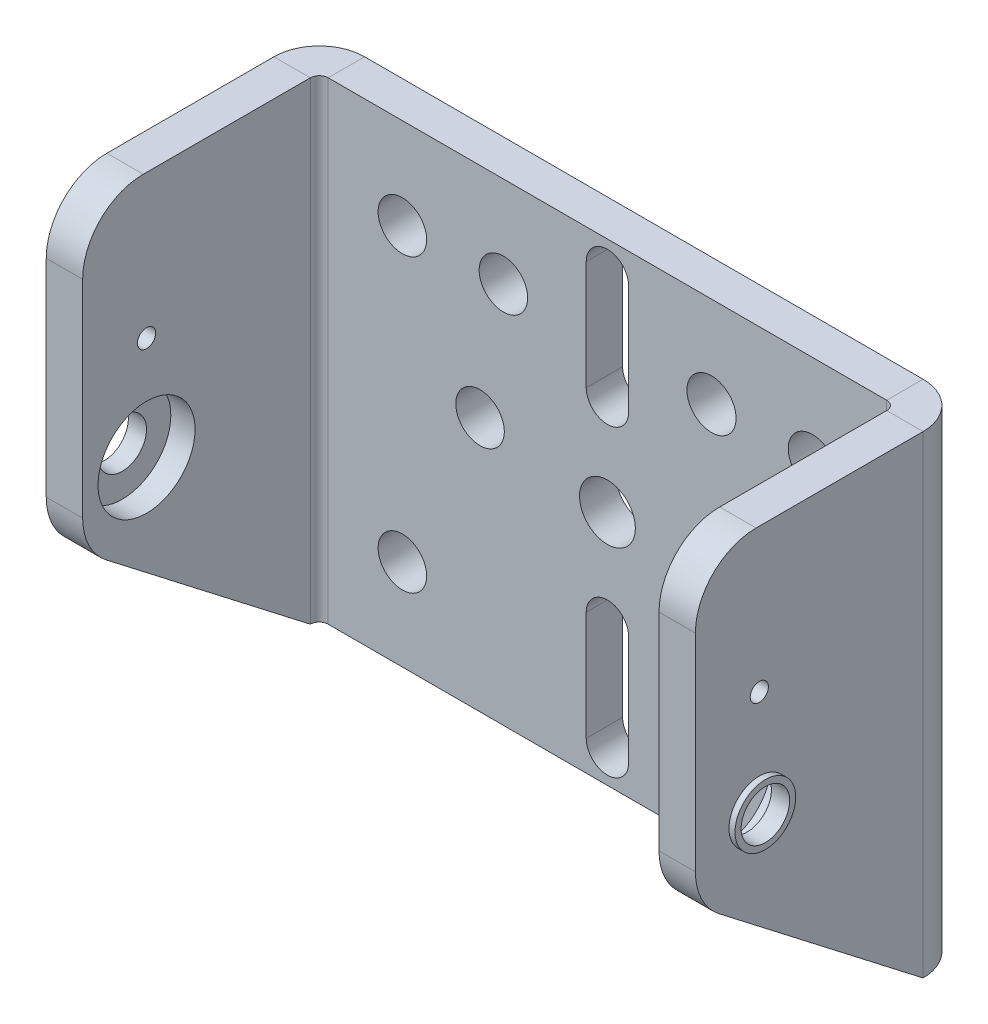
SolidWorks part; units mm, degrees
note: The reader was unsure of these and kept them because the rebuilt part matched: flange length of "Aresta-Flange1".
ref_plane "Plano frontal" through (0, 0, 0) normal (0, 0, 1) x (1, 0, 0)
ref_plane "Plano superior" through (0, 0, 0) normal (0, 1, 0) x (1, 0, 0)
ref_plane "Plano direito" through (0, 0, 0) normal (1, 0, 0) x (0, 0, -1)
sketch "Esboço1" plane through (0, 0, 0) normal (0, 0, 1) x (1, 0, 0)
  line L1 (-20.5063, 15.0091) -> (26.9937, 15.0091)
  line L2 (-20.5063, 15.0091) -> (-20.5063, -23.9909)
  line L3 (-20.5063, -23.9909) -> (26.9937, -23.9909)
  line L4 (26.9937, 15.0091) -> (26.9937, -23.9909)
  dimension "D1" = 47.5
  dimension "D2" = 39
base flange "Flange-base1" sketch "Esboço1" thickness 3 reverse thickness direction no parameters "D1"=0.7366
sketch "Esboço6" plane through (0, 0, 0) normal (0, 0, 1) x (1, 0, 0)
  line L1 (-13.6563, 7.5091) -> (20.1437, 7.5091)
  line L2 (-13.6563, 7.5091) -> (-13.6563, -16.4909)
  line L3 (-13.6563, -16.4909) -> (20.1437, -16.4909)
  line L4 (20.1437, 7.5091) -> (20.1437, -16.4909)
  line L6 (26.9937, 15.0091) -> (-20.5063, 15.0091) construction
  line L7 (-20.5063, -23.9909) -> (26.9937, -23.9909) construction
  line L8 (3.2437, 15.0091) -> (3.2437, -23.9909) construction
  line L9 (3.2437, 3.5238) -> (3.2437, 12.5238) construction
  line L10 (1.4937, 3.5238) -> (1.4937, 12.5238)
  line L11 (4.9937, 3.5238) -> (4.9937, 12.5238)
  line L12 (-20.5063, -4.4909) -> (26.9937, -4.4909) construction
  line L13 (-20.5063, 15.0091) -> (-20.5063, -23.9909) construction
  line L14 (26.9937, -23.9909) -> (26.9937, 15.0091) construction
  line L15 (3.2437, -12.5057) -> (3.2437, -21.5057) construction
  line L16 (1.4937, -12.5057) -> (1.4937, -21.5057)
  line L17 (4.9937, -12.5057) -> (4.9937, -21.5057)
  circle A0 centre (-13.6563, 7.5091) radius 2
  circle A1 centre (-13.6563, -16.4909) radius 2
  circle A2 centre (20.1437, -16.4909) radius 2
  circle A3 centre (20.1437, 7.5091) radius 2
  circle A4 centre (3.2437, -4.4909) radius 2.3
  arc A5 (1.4937, 3.5238) -> (4.9937, 3.5238) centre (3.2437, 3.5238) ccw
  arc A6 (4.9937, 12.5238) -> (1.4937, 12.5238) centre (3.2437, 12.5238) ccw
  arc A7 (1.4937, -12.5057) -> (4.9937, -12.5057) centre (3.2437, -12.5057) cw
  arc A8 (4.9937, -21.5057) -> (1.4937, -21.5057) centre (3.2437, -21.5057) cw
  point P18 (3.2437, 8.0238)
  point P31 (3.2437, -17.0057)
  dimension "D1" = 6.85
  dimension "D3" = 7.5
  dimension "D4" = 7.5
extrude "Corte-extrusão1" cut sketch "Esboço6" against normal blind 10 contours L1 A0 L2 | L2 A0 L1 | L2 A1 L3 | L3 A1 L2 | A4 | L10 A5 L11 L1 | L11 A6 L10 L1 | A7 L16 L3 L17 | A8 L17 L3 L16 | A2 L3 L4 | A2 L4 L3 | A3 L4 L1 | A3 L1 L4 normal cut yes
edge flange "Aresta-Flange1" sketch "Esboço11" flange profiles "Esboço11", "Esboço12" flange angle 90 flange length 22.5 flange position material outside bend radius 0.7366 thickness 3 parameters "D6"=10, "D8"=1
sketch "Esboço11" plane through (26.9937, 0, 0) normal (1, 0, 0) x (0, 1, 0)
  line L0 (-23.9909, 0) -> (15.0091, 0) construction
  line L1 (-23.9909, 0) -> (15.0091, 0)
  line L2 (-23.9909, 0) -> (-23.9909, 19.5)
  line L3 (-23.9909, 19.5) -> (15.0091, 19.5)
  line L4 (15.0091, 19.5) -> (15.0091, 0)
  dimension "D1" = 19.5
sketch "Esboço12" plane through (-20.5063, 0, 0) normal (-1, 0, 0) x (0, -1, 0)
  line L0 (-15.0091, 0) -> (23.9909, 0) construction
  line L1 (-15.0091, 0) -> (23.9909, 0)
  line L2 (-15.0091, 0) -> (-15.0091, 19.5)
  line L3 (-15.0091, 19.5) -> (23.9909, 19.5)
  line L4 (23.9909, 19.5) -> (23.9909, 0)
bend "DobradeAresta1" bend radius 0.7366 bend angle 90 parameters "D5"=1
bend "DobradeAresta2" bend radius 0.7366 bend angle 90 parameters "D5"=2
sketch "Esboço13" plane through (-23.5063, 0, 0) normal (-1, 0, 0) x (0, 0, 1)
  line L0 (0.7366, -23.9909) -> (19.5, -9.4909) construction
  line L1 (19.5, -23.9909) -> (19.5, 15.0091) construction
  line L2 (19.5, -9.4909) -> (0.7366, 15.0091) construction
  line L3 (0.7366, -23.9909) -> (19.5, -23.9909)
  line L4 (19.5, -23.9909) -> (19.5, -9.4909)
  line L5 (19.5, -9.4909) -> (0.7366, -23.9909)
  circle A0 centre (14.2347, -5.3252) radius 2
  circle A1 centre (14.2347, 3.1748) radius 0.75
  point P12 (7.6691, -1.6999)
  dimension "D3" = 4
  dimension "D4" = 1.5
  dimension "D1" = 14.5
  dimension "D2" = 5.2653
  dimension "D5" = 8.5
  dimension "D7" = 7.5
extrude "Corte-extrusão2" cut sketch "Esboço13" against normal blind 70 normal cut yes
fillet "Filete1" radius 5 4 edges at (28.4937, -9.4909, 19.5) (28.4937, 15.0091, 19.5) (-22.0063, -9.4909, 19.5) (-22.0063, 15.0091, 19.5)
sketch "Esboço14" plane through (0, 0, 0) normal (0, 0, 1) x (1, 0, 0)
  line L0 (-13.6563, 7.5091) -> (20.1437, 7.5091) construction
  line L1 (3.2437, 12.5238) -> (3.2437, -4.4909) construction
  line L2 (26.2571, 15.0091) -> (-19.7697, 15.0091) construction
  circle A0 centre (-5.3313, 7.5091) radius 1.9979
  circle A1 centre (11.8187, 7.5091) radius 2.0261
  circle A2 centre (13.7437, -2.9909) radius 2
  circle A3 centre (-7.2563, -2.9909) radius 2
  dimension "D2" = 18
  dimension "D1" = 17.15
  dimension "D3" = 21
extrude "Corte-extrusão4" cut sketch "Esboço14" against normal blind 3 normal cut yes
sketch "Sketch1" plane through (-23.5063, 0, 0) normal (-1, 0, 0) x (0, 0, 1)
  circle A0 centre (14.2347, -5.3252) radius 2.5
  circle A2 centre (14.2347, -5.3252) radius 2
  circle A3 centre (14.2347, -5.3252) radius 2 construction
  dimension "D1" = 0.5
extrude "Boss-Extrude1" add sketch "Sketch1" along normal blind 0.5
sketch "Sketch2" plane through (-20.5063, 0, 0) normal (1, 0, 0) x (0, 0, -1)
  circle A0 centre (-14.2347, -5.3252) radius 4
  dimension "D1" = 8
extrude "Cut-Extrude8" cut sketch "Sketch2" against normal blind 2 normal cut yes
ref_plane "Plane1" through (3.2437, 0, 0) normal (-1, 0, 0) x (0, -1, 0)
mirror "Mirror1" about plane through (3.2437, 0, 0) normal (-1, 0, 0) of "Boss-Extrude1", "Cut-Extrude8"
sketch "Curva-Linhas1" [suppressed] plane through (0, 0, 0) normal (0, 1, 0) x (1, 0, 0)
sketch "Caixa delimitadora1" [suppressed] plane through (0, 0, 0) normal (0, 1, 0) x (1, 0, 0)
sheet metal parameters "Chapa metálica1" thickness 3 parameters "D1"=0.7366
flat pattern "Padrão-Plano1" [suppressed]
sketch "Curva-Linhas2" plane through (0, 0, 0) normal (0, 1, 0) x (1, 0, 0)
sketch3d "Caixa delimitadora2" [suppressed]
  line L0 (21.0063, -23.9909, 0) -> (-26.9937, -23.9909, 0) construction
  line L1 (21.0063, 15.0091, 0) -> (-26.9937, 15.0091, 0) construction
  line L2 (21.0063, -23.9909, 0) -> (21.0063, 15.0091, 0) construction
  line L3 (-26.9937, -23.9909, 0) -> (-26.9937, 15.0091, 0) construction
sheet metal parameters "Chapa metálica2" thickness 3 parameters "D1"=0.7366
flat pattern "Padrão-Plano1"
sketch "Curva-Linhas2" plane through (0, 0, 0) normal (0, 1, 0) x (1, 0, 0)
sketch3d "Caixa delimitadora2" [suppressed]
  line L0 (-21.0063, -23.9909, 0) -> (26.9937, -23.9909, 0) construction
  line L1 (-21.0063, 15.0091, 0) -> (26.9937, 15.0091, 0) construction
  line L2 (-21.0063, -23.9909, 0) -> (-21.0063, 15.0091, 0) construction
  line L3 (26.9937, -23.9909, 0) -> (26.9937, 15.0091, 0) construction
sheet metal parameters "Chapa metálica3" thickness 3 parameters "D1"=0.7366
flat pattern "Padrão-Plano1"
sketch "Curva-Linhas2" plane through (0, 0, 0) normal (0, 0, 1) x (1, 0, 0)
  line L0 (-22.0263, 15.0091) -> (-22.0263, -23.9909) construction
  line L1 (28.0138, -23.9909) -> (28.0138, 15.0091) construction
  line L2 (-22.0263, 15.0091) -> (-22.0263, -23.9909) construction
  line L3 (28.0138, -23.9909) -> (28.0138, 15.0091) construction
sketch3d "Caixa delimitadora2" [suppressed]
  line L0 (-50.0463, -23.9909, 0) -> (56.0338, -23.9909, 0) construction
  line L1 (-50.0463, 15.0091, 0) -> (56.0338, 15.0091, 0) construction
  line L2 (-50.0463, -23.9909, 0) -> (-50.0463, 15.0091, 0) construction
  line L3 (56.0338, -23.9909, 0) -> (56.0338, 15.0091, 0) construction
bend of the flat pattern "Planificar-<DobradeAresta1>1"
bend of the flat pattern "Planificar-<DobradeAresta2>1"
sheet metal parameters "Chapa metálica4" thickness 3 parameters "D1"=0.7366
flat pattern "Padrão-Plano1"
sketch "Curva-Linhas2" plane through (0, 0, 0) normal (0, 0, 1) x (1, 0, 0)
  line L0 (-22.0263, 15.0091) -> (-22.0263, -23.9909) construction
  line L1 (28.0138, -23.9909) -> (28.0138, 15.0091) construction
  line L2 (-22.0263, 15.0091) -> (-22.0263, -23.9909) construction
  line L3 (28.0138, -23.9909) -> (28.0138, 15.0091) construction
sketch3d "Caixa delimitadora2" [suppressed]
  line L0 (-50.0463, -23.9909, 0) -> (56.0338, -23.9909, 0) construction
  line L1 (-50.0463, 15.0091, 0) -> (56.0338, 15.0091, 0) construction
  line L2 (-50.0463, -23.9909, 0) -> (-50.0463, 15.0091, 0) construction
  line L3 (56.0338, -23.9909, 0) -> (56.0338, 15.0091, 0) construction
bend of the flat pattern "Planificar-<DobradeAresta1>1"
bend of the flat pattern "Planificar-<DobradeAresta2>1"
sheet metal parameters "Chapa metálica6" thickness 3 parameters "D1"=0.7366
flat pattern "Padrão-Plano1"
sketch "Curva-Linhas2" plane through (0, 0, 0) normal (0, 0, 1) x (1, 0, 0)
  line L0 (-22.0263, 15.0091) -> (-22.0263, -23.9909) construction
  line L1 (28.0138, -23.9909) -> (28.0138, 15.0091) construction
  line L2 (-22.0263, 15.0091) -> (-22.0263, -23.9909) construction
  line L3 (28.0138, -23.9909) -> (28.0138, 15.0091) construction
sketch3d "Caixa delimitadora2" [suppressed]
  line L0 (-40.0463, -23.9909, 0) -> (46.0338, -23.9909, 0) construction
  line L1 (-40.0463, 15.0091, 0) -> (46.0338, 15.0091, 0) construction
  line L2 (-40.0463, -23.9909, 0) -> (-40.0463, 15.0091, 0) construction
  line L3 (46.0338, -23.9909, 0) -> (46.0338, 15.0091, 0) construction
bend of the flat pattern "Planificar-<DobradeAresta1>1"
bend of the flat pattern "Planificar-<DobradeAresta2>1"
sheet metal parameters "Chapa metálica7" thickness 3 parameters "D1"=0.7366
flat pattern "Padrão-Plano1"
sketch "Curva-Linhas2" plane through (0, 0, 0) normal (0, 0, 1) x (1, 0, 0)
  line L0 (-22.0263, 15.0091) -> (-22.0263, -23.9909) construction
  line L1 (28.0138, -23.9909) -> (28.0138, 15.0091) construction
  line L2 (-22.0263, 15.0091) -> (-22.0263, -23.9909) construction
  line L3 (28.0138, -23.9909) -> (28.0138, 15.0091) construction
sketch3d "Caixa delimitadora2" [suppressed]
  line L0 (-40.0463, -23.9909, 0) -> (46.0338, -23.9909, 0) construction
  line L1 (-40.0463, 15.0091, 0) -> (46.0338, 15.0091, 0) construction
  line L2 (-40.0463, -23.9909, 0) -> (-40.0463, 15.0091, 0) construction
  line L3 (46.0338, -23.9909, 0) -> (46.0338, 15.0091, 0) construction
bend of the flat pattern "Planificar-<DobradeAresta1>1"
bend of the flat pattern "Planificar-<DobradeAresta2>1"
sheet metal parameters "Chapa metálica8" thickness 3 parameters "D1"=0.7366
flat pattern "Padrão-Plano1"
sketch "Curva-Linhas2" plane through (0, 0, 0) normal (0, 0, 1) x (1, 0, 0)
  line L0 (-22.0263, 15.0091) -> (-22.0263, -23.9909) construction
  line L1 (28.0138, -23.9909) -> (28.0138, 15.0091) construction
  line L2 (-22.0263, 15.0091) -> (-22.0263, -23.9909) construction
  line L3 (28.0138, -23.9909) -> (28.0138, 15.0091) construction
sketch3d "Caixa delimitadora2" [suppressed]
  line L0 (-40.0463, -23.9909, 0) -> (46.0338, -23.9909, 0) construction
  line L1 (-40.0463, 15.0091, 0) -> (46.0338, 15.0091, 0) construction
  line L2 (-40.0463, -23.9909, 0) -> (-40.0463, 15.0091, 0) construction
  line L3 (46.0338, -23.9909, 0) -> (46.0338, 15.0091, 0) construction
bend of the flat pattern "Planificar-<DobradeAresta1>1"
bend of the flat pattern "Planificar-<DobradeAresta2>1"
sheet metal parameters "Chapa metálica10" thickness 3 parameters "D1"=0.7366
flat pattern "Padrão-Plano1"
sketch "Curva-Linhas2" plane through (0, 0, 0) normal (0, 0, 1) x (1, 0, 0)
  line L0 (-21.5263, 15.0091) -> (-21.5263, -23.9909) construction
  line L1 (28.0138, -23.9909) -> (28.0138, 15.0091) construction
  line L2 (-21.5263, 15.0091) -> (-21.5263, -23.9909) construction
  line L3 (28.0138, -23.9909) -> (28.0138, 15.0091) construction
sketch3d "Caixa delimitadora2" [suppressed]
  line L0 (-42.0463, -23.9909, 0) -> (48.5338, -23.9909, 0) construction
  line L1 (-42.0463, 15.0091, 0) -> (48.5338, 15.0091, 0) construction
  line L2 (-42.0463, -23.9909, 0) -> (-42.0463, 15.0091, 0) construction
  line L3 (48.5338, -23.9909, 0) -> (48.5338, 15.0091, 0) construction
bend of the flat pattern "Planificar-<DobradeAresta1>1"
bend of the flat pattern "Planificar-<DobradeAresta2>1"
